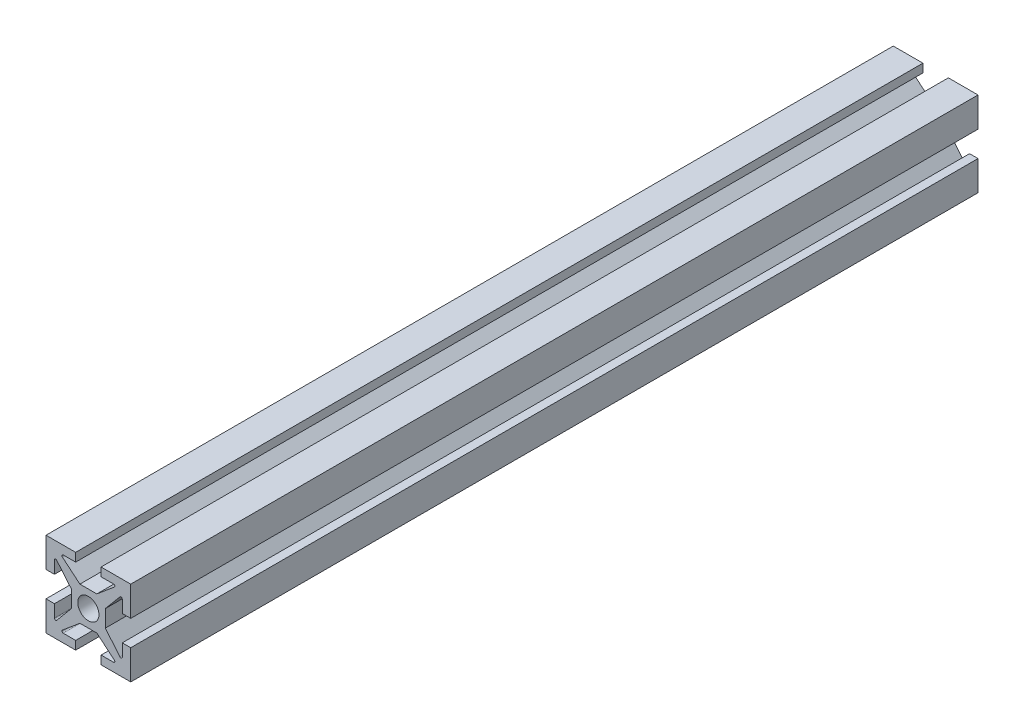
SolidWorks part; units mm, degrees
ref_plane "Front Plane" through (0, 0, 0) normal (0, 0, 1) x (1, 0, 0)
ref_plane "Top Plane" through (0, 0, 0) normal (0, 1, 0) x (1, 0, 0)
ref_plane "Right Plane" through (0, 0, 0) normal (1, 0, 0) x (0, 0, -1)
sketch "Esquisse1" plane through (0, 0, 0) normal (0, 0, 1) x (1, 0, 0)
  line L0 (0, 2) -> (0, 1.25)
  line L1 (-3.0678, 3.7351) -> (-1, 2)
  line L2 (-2.9714, 4) -> (-1.5, 4)
  line L3 (-1.5, 4) -> (-1.5, 5)
  line L4 (-5, 5) -> (-5, 1.5)
  line L5 (-5, 1.5) -> (-4, 1.5)
  line L6 (-4, 1.5) -> (-4, 2.9714)
  line L7 (-5, 5) -> (-1.5, 5)
  line L8 (-3.7351, 3.0678) -> (-2, 1)
  line L9 (-2, 1) -> (-2, 0)
  line L10 (-2, 0) -> (-1.25, 0)
  line L11 (-1, 2) -> (0, 2)
  arc A0 (-2.9714, 4) -> (-3.0678, 3.7351) centre (-2.9714, 3.85) ccw
  arc A1 (-4, 2.9714) -> (-3.7351, 3.0678) centre (-3.85, 2.9714) cw
  arc A2 (0, 1.25) -> (-1.25, 0) centre (0, 0) ccw
  dimension "D7" = 0.15
  dimension "D4" = 1.25
  dimension "D1" = 3.5
  dimension "D2" = 1
  dimension "D3" = 1
  dimension "D5" = 5
  dimension "D6" = 2
  dimension "D8" = 5
  dimension "D9" = 40
ref_axis "Axe1" through (0, -0.1269, 0) along (0, 1, 0)
extrude "Boss.-Extru.1" add sketch "Esquisse1" along normal blind 100
ref_axis "Axe2" through (0, 0, 105) along (0, 0, -1)
pattern_circular "Répétition circulaire1" count 4 every 90 about axis through (0, 0, 105) along (0, 0, -1) of "Boss.-Extru.1"
